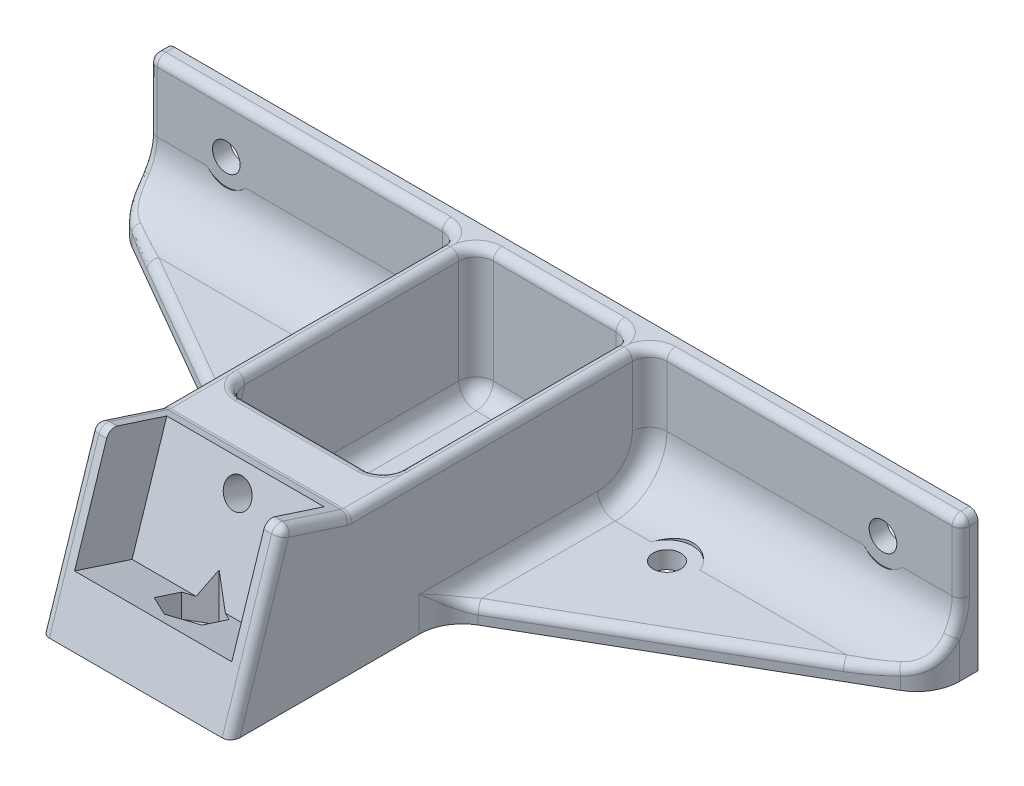
SolidWorks part; units mm, degrees
material "ABS"
ref_plane "Front" through (0, 0, 0) normal (0, 0, 1) x (1, 0, 0)
ref_plane "Top" through (0, 0, 0) normal (0, 1, 0) x (1, 0, 0)
ref_plane "Right" through (0, 0, 0) normal (1, 0, 0) x (0, 0, -1)
sketch "Esquisse1" plane through (0, 0, 0) normal (0, 1, 0) x (1, 0, 0)
  line L1 (0, 0) -> (47, 0)
  line L6 (0, -60) -> (11, -60)
  line L8 (11, -25.7846) -> (11, -60)
  line L9 (47, 0) -> (47, -5)
  line L10 (47, -5) -> (11, -25.7846)
  line L12 (0, 0) -> (0, -60)
  circle A1 centre (20, -9) radius 1.6
  dimension "D3" = 9
  dimension "D4" = 5
  dimension "D5" = 30
  dimension "D2" = 20
  dimension "D8" = 3.2
  dimension "D1" = 47
  dimension "D6" = 60
  dimension "D7" = 11
extrude "Boss.-Extru.1" add sketch "Esquisse1" along normal blind 16
fillet "Congé1" radius 5 2 edges at (11, 8, 25.7846) (47, 8, 5)
sketch "Esquisse2" plane through (0, 0, 0) normal (0, 0, -1) x (-1, 0, 0)
  line L2 (-47, 0) -> (0, 0) construction
  circle A0 centre (-38, 10) radius 1.6
  dimension "D1" = 3.2
  dimension "D2" = 38
  dimension "D3" = 10
extrude "Enlèv. mat.-Extru.1" cut sketch "Esquisse2" against normal through all
sketch "Esquisse3" plane through (0, 0, 0) normal (0, 0, -1) x (-1, 0, 0)
  circle A0 centre (-38, 10) radius 3
  circle A2 centre (-38, 10) radius 1.6 construction
  dimension "D1" = 6
extrude "Enlèv. mat.-Extru.2" cut sketch "Esquisse3" against normal through all from offset 2 offset against normal yes
sketch "Esquisse4" plane through (11, 0, 0) normal (1, 0, 0) x (0, 0, -1)
  line L0 (-60, 0) -> (-28.6714, 0) construction
  line L1 (-60, 16) -> (-2, 16)
  line L2 (-60, 16) -> (-60, 2)
  line L3 (-60, 2) -> (-8, 2)
  line L4 (-2, 16) -> (-2, 8)
  line L5 (0, 16) -> (0, 0) construction
  arc A0 (-8, 2) -> (-2, 8) centre (-8, 8) ccw
  dimension "D2" = 6
  dimension "D1" = 2
  dimension "D3" = 2
extrude "Enlèv. mat.-Extru.3" cut sketch "Esquisse4" along normal through all
sketch "Esquisse6" plane through (11, 0, 0) normal (1, 0, 0) x (0, 0, -1)
  line L0 (-60, 16) -> (-2, 16) construction
  line L1 (-60, 0) -> (-50.4702, 0)
  line L2 (-60, 0) -> (-60, 16)
  line L3 (-60, 16) -> (-45.2715, 16)
  line L4 (-50.4702, 0) -> (-45.2715, 16)
  dimension "D1" = 18
  dimension "D2" = 48
extrude "Enlèv. mat.-Extru.5" cut sketch "Esquisse6" against normal through all
fillet "Congé2" radius 2 3 edges at (11, 2, 18.3357) (11, 3.7574, 3.7574) (11, 12, 2)
sketch "Esquisse11" plane through (0, 0, 0) normal (-1, 0, 0) x (0, 0, 1)
  line L0 (45.2715, 16) -> (36.6098, 16)
  line L1 (0, 16) -> (45.2715, 16) construction
  line L2 (36.6098, 16) -> (44.4444, 18.5456)
  line L3 (50.4702, 0) -> (45.2715, 16) construction
  line L4 (44.4444, 18.5456) -> (45.2715, 16)
  dimension "D1" = 8.2377
  dimension "D2" = 19.5
extrude "Boss.-Extru.2" add sketch "Esquisse11" against normal up to surface (11 mm away) up to face at (11, 6.7388, 24.0366)
fillet "Congé3" radius 1 9 edges at (11.5111, 2.6647, 26.4692) (46.6313, 3.5299, 3.9978) (43.1636, 2.0516, 7.2149) (27.6519, 2, 16.1706) (5.5, 18.5456, 44.4444) (5.5, 16, 36.6098) (47, 12, 2) (47, 7.4171, 2.0284) (13.2451, 2, 24.4988)
sketch "Esquisse5" plane through (0, 0, 0) normal (0, -1, 0) x (1, 0, 0)
  circle A0 centre (20, 9) radius 3
  dimension "D1" = 6
extrude "Enlèv. mat.-Extru.4" cut sketch "Esquisse5" against normal through all from offset 2 offset against normal yes
sketch "Esquisse7" plane through (0, 14.8328, 45.6507) normal (0, 0.309, 0.9511) x (1, 0, 0)
  line L1 (9.1, -9.0961) -> (0, -9.0961)
  line L2 (9.1, -9.0961) -> (9.1, 15.2169)
  line L3 (9.1, 15.2169) -> (0, 15.2169)
  line L4 (0, -9.0961) -> (0, 15.2169)
  line L5 (0, -15.5961) -> (11, -15.5961) construction
  dimension "D1" = 9.1
  dimension "D2" = 6.5
extrude "Enlèv. mat.-Extru.6" cut sketch "Esquisse7" against normal blind 7
sketch "Esquisse8" plane through (0, 12.6697, 38.9933) normal (0, 0.309, 0.9511) x (1, 0, 0)
  line L0 (0, -9.0961) -> (9.1, -9.0961) construction
  line L2 (0, -15.5961) -> (0, -9.0961) construction
  circle A0 centre (0, 1.0039) radius 1.6
  dimension "D1" = 10.1
  dimension "D2" = 3.2
extrude "Enlèv. mat.-Extru.7" cut sketch "Esquisse8" against normal blind 9
sketch "Esquisse10" plane through (0, 0, 0) normal (-1, 0, 0) x (0, 0, 1)
  line L0 (41.8042, 4.0187) -> (37.787, 16.3825) construction
  line L1 (2, 16) -> (30.551, 16)
  line L2 (2, 16) -> (2, 1)
  line L3 (2, 1) -> (33.4753, 1)
  line L4 (30.551, 16) -> (33.4753, 7)
  line L5 (0, 16) -> (36.4514, 16) construction
  line L6 (41.8042, 4.0187) -> (37.787, 16.3825) construction
  line L7 (0, 16) -> (0, 0) construction
  line L8 (0, 0) -> (50.4702, 0) construction
  line L11 (33.4753, 7) -> (33.4753, 1)
  dimension "D1" = 7
  dimension "D2" = 2
  dimension "D3" = 1
  dimension "D4" = 7
  dimension "D5" = 90
extrude "Enlèv. mat.-Extru.8" cut sketch "Esquisse10" against normal up to surface (9.1 mm away) up to face at (9.1, 12.535, 43.2865)
fillet "Congé4" radius 2 7 edges at (9.1, 11.5, 32.0131) (9.1, 1, 17.7376) (9.1, 8.5, 2) (4.55, 1, 2) (4.55, 1, 33.4753) (4.55, 7, 33.4753) (9.1, 4, 33.4753)
sketch "Esquisse12" plane through (0, 10.5066, 32.3359) normal (0, -0.309, -0.9511) x (-1, 0, 0)
  line L1 (0, -2.1716) -> (2.75, -0.5839)
  line L2 (2.75, -0.5839) -> (2.75, 2.5916)
  line L3 (2.75, 2.5916) -> (0, 4.1793)
  line L4 (0, 4.1793) -> (-2.75, 2.5916)
  line L5 (-2.75, 2.5916) -> (-2.75, -0.5839)
  line L6 (-2.75, -0.5839) -> (0, -2.1716)
  circle A0 centre (0, 1.0039) radius 2.75 construction
  arc A1 (0, 2.6039) -> (0, -0.5961) centre (0, 1.0039) ccw construction
  dimension "D1" = 5.5
extrude "Enlèv. mat.-Extru.9" cut sketch "Esquisse12" against normal blind 3
fillet "Congé6" radius 1 14 edges at (3.55, 16, 30.551) (8.5142, 16, 29.9351) (9.1, 16, 16.224) (8.5142, 16, 2.5858) (47, 16, 0.5) (11, 8.7973, 47.6118) (11, 18.1765, 44.2563) (11, 17.1428, 40.1269) (11, 16.0123, 36.6078) (11, 16, 20.2257) (11.5858, 16, 2.5858) (3.55, 16, 2) (29.5, 16, 2) (46.7071, 16, 1.7071)
sketch "Esquisse13" plane through (0, 0, 0) normal (0, -1, 0) x (1, 0, 0)
  line L0 (0, 0) -> (0, 50.4702) construction
  line L1 (47, 0) -> (0, 0) construction
  circle A0 centre (0, 44) radius 1.6
  dimension "D1" = 3.2
  dimension "D2" = 44
extrude "Enlèv. mat.-Extru.10" cut sketch "Esquisse13" against normal blind 4
sketch "Esquisse14" plane through (0, 0, 0) normal (0, -1, 0) x (1, 0, 0)
  line L1 (2.75, 42.4123) -> (2.75, 45.5877)
  line L2 (2.75, 45.5877) -> (0, 47.1754)
  line L3 (0, 47.1754) -> (-2.75, 45.5877)
  line L4 (-2.75, 45.5877) -> (-2.75, 42.4123)
  line L5 (-2.75, 42.4123) -> (0, 40.8246)
  line L6 (0, 40.8246) -> (2.75, 42.4123)
  circle A0 centre (0, 44) radius 2.75 construction
  arc A1 (0, 42.4) -> (0, 45.6) centre (0, 44) ccw construction
  dimension "D1" = 5.5
extrude "Enlèv. mat.-Extru.11" cut sketch "Esquisse14" against normal blind 6 from offset 1.5 offset against normal yes
mirror "Symétrie1" about plane through (0, 16, 0) normal (1, 0, 0) of bodies 113
sketch "Esquisse16" plane through (0, 0, 0) normal (0, -1, 0) x (1, 0, 0)
  line L8 (10, 50.4702) -> (-10, 50.4702)
  line L9 (-11, 49.4187) -> (-11, 28.6714)
  line L10 (-13.5, 24.3412) -> (-44.5, 6.4434)
  line L11 (-47, 2.1132) -> (-47, 0)
  line L12 (-47, 0) -> (47, 0)
  line L13 (47, 0) -> (47, 2.1132)
  line L14 (44.5, 6.4434) -> (13.5, 24.3412)
  line L15 (11, 28.6714) -> (11, 49.4187)
  line L16 (10, 50.4702) -> (-10, 50.4702)
  line L17 (-11, 49.4187) -> (-11, 28.6714)
  line L18 (-13.5, 24.3412) -> (-44.5, 6.4434)
  line L19 (-47, 2.1132) -> (-47, 0)
  line L20 (-47, 0) -> (47, 0)
  line L21 (47, 0) -> (47, 2.1132)
  line L22 (44.5, 6.4434) -> (13.5, 24.3412)
  line L23 (11, 28.6714) -> (11, 49.4187)
  arc A4 (-13.5, 24.3412) -> (-11, 28.6714) centre (-16, 28.6714) ccw
  arc A5 (-44.5, 6.4434) -> (-47, 2.1132) centre (-42, 2.1132) ccw
  arc A6 (47, 2.1132) -> (44.5, 6.4434) centre (42, 2.1132) ccw
  arc A7 (11, 28.6714) -> (13.5, 24.3412) centre (16, 28.6714) ccw
  arc A8 (-13.5, 24.3412) -> (-11, 28.6714) centre (-16, 28.6714) ccw
  arc A9 (-44.5, 6.4434) -> (-47, 2.1132) centre (-42, 2.1132) ccw
  arc A10 (47, 2.1132) -> (44.5, 6.4434) centre (42, 2.1132) ccw
  arc A11 (11, 28.6714) -> (13.5, 24.3412) centre (16, 28.6714) ccw
  ellipse E2 centre (-10, 49.4187) end of major axis (-10, 48.3673) minor radius 1 (-10, 50.4702) -> (-11, 49.4187) ccw
  ellipse E3 centre (10, 49.4187) end of major axis (10, 48.3673) minor radius 1 (11, 49.4187) -> (10, 50.4702) ccw
  ellipse E4 centre (-10, 49.4187) end of major axis (-10, 48.3673) minor radius 1 (-10, 50.4702) -> (-11, 49.4187) ccw
  ellipse E5 centre (10, 49.4187) end of major axis (10, 48.3673) minor radius 1 (11, 49.4187) -> (10, 50.4702) ccw
  dimension "D1" = 0
extrude "Boss.-Extru.3" [suppressed] add sketch "Esquisse16" against normal blind 0.2
fillet "Congé7" [suppressed] radius 0.2
